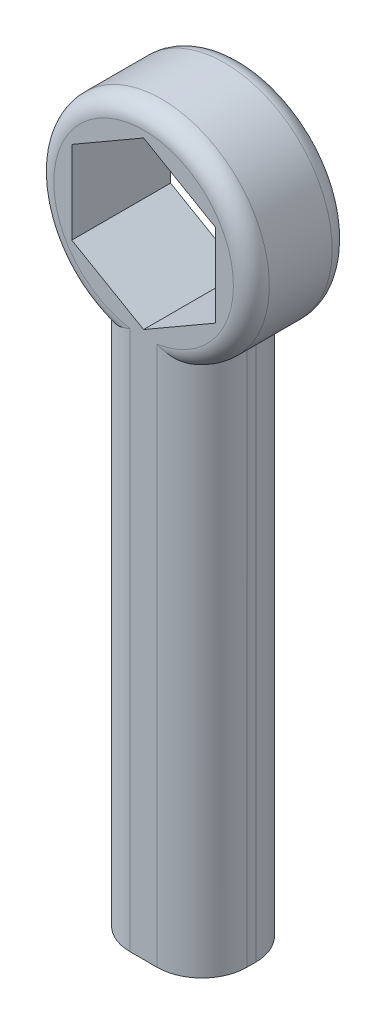
SolidWorks part; units mm, degrees
material "6061 Alloy"
ref_plane "Front Plane" through (0, 0, 0) normal (0, 0, 1) x (1, 0, 0)
ref_plane "Top Plane" through (0, 0, 0) normal (0, 1, 0) x (1, 0, 0)
ref_plane "Right Plane" through (0, 0, 0) normal (1, 0, 0) x (0, 0, -1)
sketch "Sketch1" plane through (0, 0, 0) normal (0, 1, 0) x (1, 0, 0)
  line L1 (-1.5, 5.5) -> (1.5, 5.5)
  line L2 (-6.5, 0.5) -> (-6.5, -0.5)
  line L3 (-1.5, -5.5) -> (1.5, -5.5)
  line L4 (6.5, 0.5) -> (6.5, -0.5)
  line L5 (-6.5, 5.5) -> (6.5, -5.5) construction
  line L6 (-6.5, -5.5) -> (6.5, 5.5) construction
  arc A0 (1.5, 5.5) -> (6.5, 0.5) centre (1.5, 0.5) cw
  arc A1 (6.5, -0.5) -> (1.5, -5.5) centre (1.5, -0.5) cw
  arc A2 (-1.5, -5.5) -> (-6.5, -0.5) centre (-1.5, -0.5) cw
  arc A3 (-1.5, 5.5) -> (-6.5, 0.5) centre (-1.5, 0.5) ccw
  point P0 (0, 0)
  dimension "D3" = 5
  dimension "D1" = 13
  dimension "D2" = 11
extrude "Boss-Extrude3" add sketch "Sketch1" along normal blind 70
sketch "Sketch3" plane through (0, 0, 5.5) normal (0, 0, 1) x (1, 0, 0)
  line L0 (-1.5, 70) -> (1.5, 70) construction
  circle A0 centre (0, 70) radius 12
extrude "Boss-Extrude4" add sketch "Sketch3" against normal through all
sketch "Sketch4" plane through (0, 0, 5.5) normal (0, 0, 1) x (1, 0, 0)
  line L1 (0, 79.2376) -> (-8, 74.6188)
  line L2 (-8, 74.6188) -> (-8, 65.3812)
  line L3 (-8, 65.3812) -> (0, 60.7624)
  line L4 (0, 60.7624) -> (8, 65.3812)
  line L5 (8, 65.3812) -> (8, 74.6188)
  line L6 (8, 74.6188) -> (0, 79.2376)
  circle A0 centre (0, 70) radius 8 construction
extrude "Cut-Extrude1" cut sketch "Sketch4" against normal through all
fillet "Fillet1" radius 2 2 edges at (0, 82, -5.5) (0, 82, 5.5)
sketch "Sketch5" plane through (0, 0, 0) normal (0, -1, 0) x (1, 0, 0)
  circle A0 centre (0, 0) radius 3
